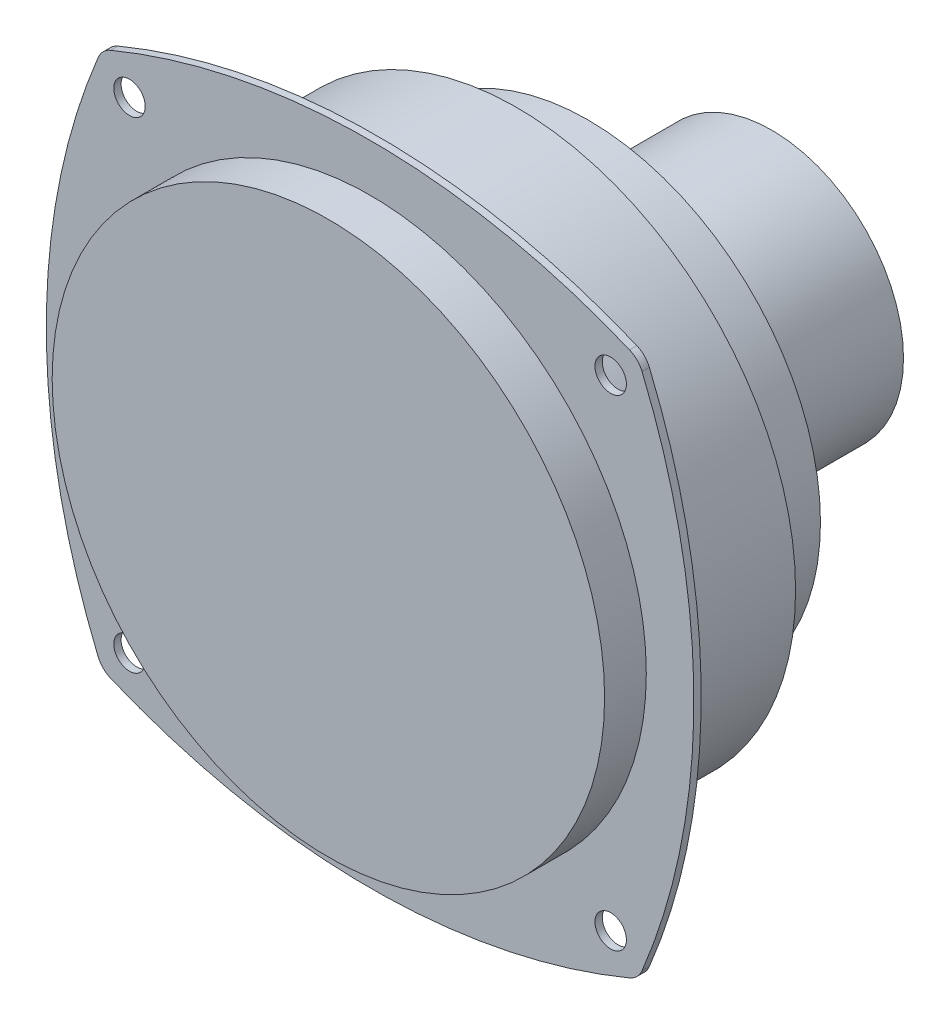
SolidWorks part; units mm, degrees
ref_plane "Front Plane" through (0, 0, 0) normal (0, 0, 1) x (1, 0, 0)
ref_plane "Top Plane" through (0, 0, 0) normal (0, 1, 0) x (1, 0, 0)
ref_plane "Right Plane" through (0, 0, 0) normal (1, 0, 0) x (0, 0, -1)
sketch "Sketch1" plane through (0, 0, 0) normal (1, 0, 0) x (0, 0, -1)
  line L0 (0, 0) -> (60.6, 0) construction
  line L1 (60.6, 0) -> (60.6, 18)
  line L2 (60.6, 18) -> (35.5, 18)
  line L3 (35.5, 18) -> (35.5, 31.75)
  line L4 (35.5, 31.75) -> (25.75, 31.75)
  line L5 (6.7, 38.1) -> (6.7, 44.25)
  line L6 (6.7, 44.25) -> (5.7, 44.25)
  line L7 (5.7, 44.25) -> (5.7, 37.75)
  line L8 (5.7, 37.75) -> (0, 37.75)
  line L9 (0, 37.75) -> (0, 0)
  line L10 (0, 0) -> (60.6, 0)
  line L11 (25.75, 38.1) -> (6.7, 38.1)
  line L12 (25.75, 31.75) -> (25.75, 38.1)
  dimension "D1" = 25.1
  dimension "D2" = 54.9
  dimension "D3" = 88.5
  dimension "D4" = 36
  dimension "D5" = 75.5
  dimension "D6" = 6.7
  dimension "D7" = 1
  dimension "D8" = 38.1
  dimension "D9" = 38.1
  dimension "D10" = 31.75
  dimension "D11" = 19.05
revolve "Revolve1" add sketch "Sketch1" angle 360 about L0
sketch "Sketch2" plane through (0, 0, -5.7) normal (0, 0, 1) x (1, 0, 0)
  line L0 (-36.4823, 36.4823) -> (36.4823, -36.4823) construction
  line L1 (-34.2372, -37.4122) -> (34.2372, -37.4122) construction
  line L2 (-37.4122, -34.2372) -> (-37.4122, 34.2372) construction
  line L3 (-34.2372, 37.4122) -> (34.2372, 37.4122) construction
  line L4 (37.4122, -34.2372) -> (37.4122, 34.2372) construction
  line L5 (0, 37.4122) -> (0, -37.4122) construction
  line L6 (-37.4122, 0) -> (37.4122, 0) construction
  arc A0 (34.2372, 37.4122) -> (37.4122, 34.2372) centre (34.2372, 34.2372) cw construction
  arc A1 (34.2372, -37.4122) -> (37.4122, -34.2372) centre (34.2372, -34.2372) ccw construction
  arc A2 (-34.2372, -37.4122) -> (-37.4122, -34.2372) centre (-34.2372, -34.2372) cw construction
  arc A3 (-37.4122, 34.2372) -> (-34.2372, 37.4122) centre (-34.2372, 34.2372) cw construction
  arc A4 (-35.4568, 37.1687) -> (35.4568, 37.1687) centre (0, -48.058) cw
  arc A6 (37.1687, 35.4568) -> (37.1687, -35.4568) centre (-48.058, 0) cw
  arc A7 (35.4568, -37.1687) -> (-35.4568, -37.1687) centre (0, 48.058) cw
  arc A8 (-37.1687, -35.4568) -> (-37.1687, 35.4568) centre (48.058, 0) cw
  arc A9 (-37.1687, 35.4568) -> (-35.4568, 37.1687) centre (-34.2372, 34.2372) cw
  arc A10 (35.4568, 37.1687) -> (37.1687, 35.4568) centre (34.2372, 34.2372) cw
  arc A11 (35.4568, -37.1687) -> (37.1687, -35.4568) centre (34.2372, -34.2372) ccw
  arc A12 (-37.1687, -35.4568) -> (-35.4568, -37.1687) centre (-34.2372, -34.2372) ccw
  circle A13 centre (0, 0) radius 44.25 construction
  point P0 (0, 0)
  point P32 (0, 0)
  dimension "D1" = 103.1875
  dimension "D2" = 3.175
extrude "Boss-Extrude1" add sketch "Sketch2" against normal up to surface (1 mm away) up to face at (44.25, 0, -6.7)
hole_wizard "Ø4.3 (4.3) Diameter Hole1" positions "Sketch4" profile "Sketch5" hole size "Ø4.3" standard "ANSI Metric" end condition through all
sketch "Sketch4" plane through (0, 0, -5.7) normal (0, 0, 1) x (1, 0, 0)
  line L0 (-32.8805, -32.8805) -> (32.8805, 32.8805) construction
  line L3 (-32.8805, 32.8805) -> (32.8805, -32.8805) construction
  circle A0 centre (0, 0) radius 46.5
  point P0 (-32.8805, 32.8805)
  point P7 (32.8805, 32.8805)
  point P9 (32.8805, -32.8805)
  point P11 (-32.8805, -32.8805)
  dimension "D1" = 93
sketch "Sketch5" plane through (-32.8805, 32.8805, -5.7) normal (1, 0, 0) x (0, -1, 0)
  line L0 (0, 0) -> (0, 54.9)
  line L1 (0, 54.9) -> (2.15, 54.9)
  line L2 (2.15, 54.9) -> (2.15, 0)
  line L5 (2.15, 0) -> (0, 0)
  line L11 (0, -6.35) -> (0, 107.95) construction
  dimension "Thru Hole Dia." = 4.3
  dimension "Thru Hole Depth" = 54.9
